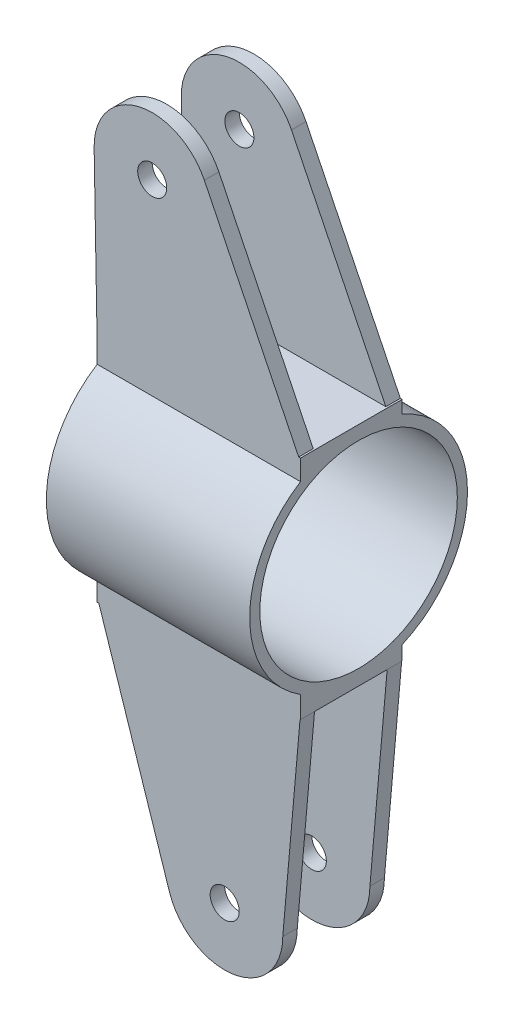
SolidWorks part; units mm, degrees
ref_plane "Front Plane" through (0, 0, 0) normal (0, 0, 1) x (1, 0, 0)
ref_plane "Top Plane" through (0, 0, 0) normal (0, 1, 0) x (1, 0, 0)
ref_plane "Right Plane" through (0, 0, 0) normal (1, 0, 0) x (0, 0, -1)
sketch "Sketch1" plane through (0, 0, 0) normal (1, 0, 0) x (0, 0, -1)
  circle A0 centre (0, 0) radius 37.5
  circle A1 centre (0, 0) radius 34
  dimension "D1" = 75
  dimension "D2" = 68
extrude "Boss-Extrude1" add sketch "Sketch1" along normal mid plane 70
sketch "Sketch2" plane through (0, 0, 0) normal (0, 0, 1) x (1, 0, 0)
  line L0 (-5.8, 94.5105) -> (-5.8, -74.5024) construction
  line L1 (35, -37.5) -> (35, 37.5) construction
  line L2 (-16.0528, 96.2387) -> (8.897, -106.9613) construction
  line L3 (-36.0464, 95.8804) -> (-35, 37.5)
  line L4 (1.9043, 105.0374) -> (35, 37.5)
  line L5 (35, 37.5) -> (-35, 37.5)
  line L8 (-35, -37.5) -> (35, -37.5)
  line L9 (-35, -37.5) -> (-10.1019, -113.2093)
  line L10 (35, -37.5) -> (28.897, -106.9613)
  circle A0 centre (-16.0528, 96.2387) radius 5
  circle A1 centre (8.897, -106.9613) radius 5
  arc A3 (-10.1019, -113.2093) -> (28.897, -106.9613) centre (8.897, -106.9613) ccw
  arc A4 (1.9043, 105.0374) -> (-36.0464, 95.8804) centre (-16.0528, 96.2387) ccw
  dimension "D3" = 10
  dimension "D4" = 10
  dimension "D7" = 40
  dimension "D1" = 40.8
  dimension "D2" = 7
  dimension "D5" = 203.2
extrude "Boss-Extrude2" add sketch "Sketch2" along normal blind 5 from offset 15 separate body
extrude "Boss-Extrude3" add sketch "Sketch2<2>" along normal blind 5 from offset 15 offset against normal yes
sketch "Sketch2<2>" plane through (0, 0, 0) normal (0, 0, 1) x (1, 0, 0) same geometry as "Sketch2"
sketch "Sketch3" plane through (35, 0, 0) normal (1, 0, 0) x (0, 0, -1)
  line L0 (-20, 37.5) -> (-20, 31.7214)
  line L2 (15, 37.5) -> (15, 34.3693)
  line L3 (-20, 38.7567) -> (15, 38.7567)
  line L4 (-15, 37.5) -> (-15, 105.0374)
  line L5 (-15, 105.0374) -> (-20, 105.0374)
  line L6 (-20, 105.0374) -> (-20, 37.5)
  line L7 (-20, 37.5) -> (-15, 37.5)
  line L10 (-20, 38.7567) -> (-20, 37.5)
  line L12 (15, 37.5) -> (15, 105.0374)
  line L13 (15, 105.0374) -> (10, 105.0374)
  line L14 (10, 105.0374) -> (10, 37.5)
  line L15 (10, 37.5) -> (15, 37.5)
  line L16 (15, 37.5) -> (15, 38.7567)
  circle A1 centre (0, 0) radius 37.5
  arc A2 (15, 34.3693) -> (-20, 31.7214) centre (0, 0) ccw
  dimension "D1" = 0
  dimension "D2" = 0
  dimension "D3" = 0
extrude "Boss-Extrude4" add sketch "Sketch3" against normal up to surface (70 mm away) up to face at (-35, 0, -37.5)
sketch "Sketch4" plane through (-35, 0, 0) normal (-1, 0, 0) x (0, 0, 1)
  line L32 (-15, -39.2326) -> (20, -39.2326)
  line L33 (-15, -34.3693) -> (-15, -39.2326)
  line L34 (20, -31.7214) -> (20, -39.2326)
  arc A0 (-15, 34.3693) -> (20, 31.7214) centre (0, 0) ccw construction
  arc A1 (-15, -34.3693) -> (20, -31.7214) centre (0, 0) ccw
extrude "Boss-Extrude5" add sketch "Sketch4" against normal up to surface (70 mm away) up to face at (35, 18.2914, 1.1678)
